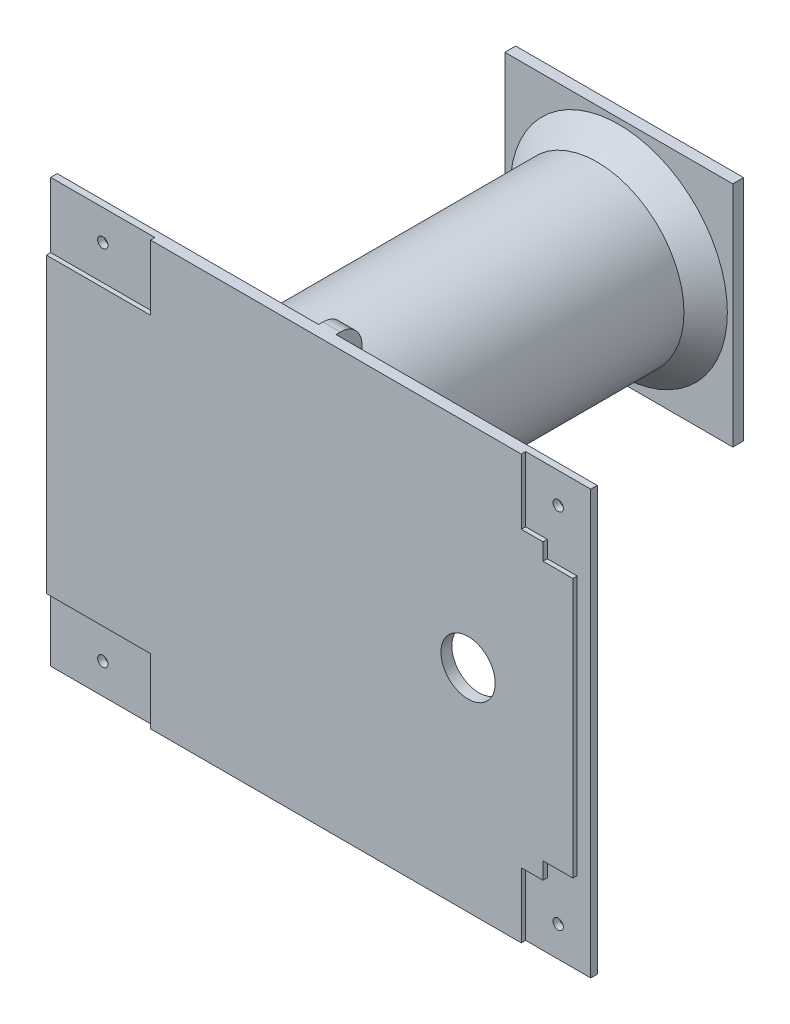
SolidWorks part; units mm, degrees
ref_plane "Alzado" through (0, 0, 0) normal (0, 0, 1) x (1, 0, 0)
ref_plane "Planta" through (0, 0, 0) normal (0, 1, 0) x (1, 0, 0)
ref_plane "Vista lateral" through (0, 0, 0) normal (1, 0, 0) x (0, 0, -1)
sketch "Croquis1" plane through (0, 0, 0) normal (0, 0, 1) x (1, 0, 0)
  line L1 (-117.2917, 97.7627) -> (131.4683, 97.7627)
  line L2 (-117.2917, 97.7627) -> (-117.2917, -97.2373)
  line L3 (-117.2917, -97.2373) -> (131.4683, -97.2373)
  line L4 (131.4683, 97.7627) -> (131.4683, -97.2373)
  dimension "D1" = 248.76
  dimension "D2" = 195
extrude "Saliente-Extruir1" add sketch "Croquis1" along normal blind 5
sketch "Croquis2" plane through (0, 0, 5) normal (0, 0, 1) x (1, 0, 0)
  line L0 (-117.2917, 0.2627) -> (131.4683, 0.2627) construction
  line L1 (-117.2917, 97.7627) -> (-117.2917, -97.2373) construction
  line L2 (131.4683, -97.2373) -> (131.4683, 97.7627) construction
  line L3 (-117.2917, -97.2373) -> (-69.2917, -97.2373)
  line L4 (-117.2917, -97.2373) -> (131.4683, -97.2373) construction
  line L5 (-69.2917, -97.2373) -> (-69.2917, -67.2373)
  line L6 (-69.2917, -67.2373) -> (-117.2917, -67.2373)
  line L7 (-117.2917, -67.2373) -> (-117.2917, -97.2373)
  line L8 (131.4683, 67.7627) -> (101.4683, 67.7627)
  line L9 (131.4683, -97.2373) -> (101.4683, -97.2373)
  line L10 (131.4683, -97.2373) -> (131.4683, -67.2373)
  line L11 (131.4683, -67.2373) -> (101.4683, -67.2373)
  line L12 (101.4683, -97.2373) -> (101.4683, -67.2373)
  line L13 (101.4683, 97.7627) -> (101.4683, 67.7627)
  line L14 (131.4683, 97.7627) -> (101.4683, 97.7627)
  line L15 (131.4683, 97.7627) -> (131.4683, 67.7627)
  line L16 (-69.2917, 67.7627) -> (-117.2917, 67.7627)
  line L17 (-69.2917, 97.7627) -> (-69.2917, 67.7627)
  line L18 (-117.2917, 97.7627) -> (-69.2917, 97.7627)
  line L19 (-117.2917, 67.7627) -> (-117.2917, 97.7627)
  dimension "D1" = 48
  dimension "D2" = 30
  dimension "D3" = 30
  dimension "D4" = 30
extrude "Cortar-Extruir1" cut sketch "Croquis2" against normal blind 2
sketch "Croquis3" plane through (0, 0, 5) normal (0, 0, 1) x (1, 0, 0)
  line L0 (-69.2917, 97.7627) -> (-117.2917, 97.7627) construction
  line L1 (116.4683, 83.7627) -> (116.4683, 67.7627) construction
  line L3 (116.4683, -83.2373) -> (116.4683, -67.2373) construction
  line L5 (131.4683, -67.2373) -> (101.4683, -67.2373) construction
  line L6 (101.4683, 67.7627) -> (131.4683, 67.7627) construction
  line L7 (-93.2917, 83.7627) -> (-93.2917, 67.7627) construction
  line L8 (-117.2917, 67.7627) -> (-69.2917, 67.7627) construction
  line L9 (-93.2917, -83.2373) -> (-93.2917, -67.2373) construction
  line L10 (-69.2917, -67.2373) -> (-117.2917, -67.2373) construction
  circle A0 centre (-93.2917, 83.7627) radius 2.375
  circle A1 centre (-93.2917, -83.2373) radius 2.375
  circle A2 centre (116.4683, 83.7627) radius 2.375
  circle A3 centre (116.4683, -83.2373) radius 2.375
  dimension "D2" = 4.75
  dimension "D3" = 4.75
  dimension "D5" = 4.75
  dimension "D6" = 4.75
  dimension "D1" = 14
  dimension "D4" = 14
  dimension "D7" = 209.76
  dimension "D8" = 16
  dimension "D9" = 16
extrude "Cortar-Extruir2" cut sketch "Croquis3" against normal blind 10
sketch "Croquis4" plane through (0, 0, 0) normal (0, 0, -1) x (-1, 0, 0)
  line L7 (-131.4683, 97.7627) -> (117.2917, 97.7627) construction
  line L9 (117.2917, 97.7627) -> (117.2917, -97.2373) construction
  circle A0 centre (55.1017, 0.2627) radius 40
  dimension "D3" = 80
  dimension "D1" = 62.19
  dimension "D2" = 97.5
extrude "Saliente-Extruir2" add sketch "Croquis4" along normal blind 196.5 contours A0
sketch "Croquis5" plane through (0, 0, 0) normal (0, 0, -1) x (-1, 0, 0)
  line L0 (-131.4683, 0.2627) -> (117.2917, 0.2627) construction
  line L1 (-131.4683, -97.2373) -> (-131.4683, 97.7627) construction
  line L2 (117.2917, 97.7627) -> (117.2917, -97.2373) construction
  circle A0 centre (-76.9683, 0.2627) radius 12.5
  dimension "D1" = 25
  dimension "D2" = 54.5
extrude "Cortar-Extruir3" cut sketch "Croquis5" against normal blind 10
sketch "Croquis6" plane through (0, 0, 0) normal (0, 0, -1) x (-1, 0, 0)
  line L0 (-131.4683, 97.7627) -> (117.2917, 97.7627) construction
  line L1 (-7.0883, 97.7627) -> (-7.0883, -97.2373)
  line L2 (117.2917, -97.2373) -> (-131.4683, -97.2373) construction
  line L3 (-7.0883, 97.7627) -> (117.2917, 97.7627)
  line L4 (117.2917, 97.7627) -> (117.2917, -97.2373)
  line L5 (117.2917, -97.2373) -> (-7.0883, -97.2373)
  line L6 (-131.4683, 0.2627) -> (56.0317, 0.2627)
  line L7 (-131.4683, -97.2373) -> (-131.4683, 97.7627) construction
  circle A1 centre (56.0317, 0.2627) radius 100
  dimension "D1" = 200
  dimension "D2" = 187.5
sketch "Croquis9" plane through (0, 97.7627, 0) normal (0, 1, 0) x (1, 0, 0)
  line L0 (7.0883, 0) -> (7.0883, -5)
  line L1 (131.4683, 0) -> (-117.2917, 0) construction
  line L2 (101.4683, -5) -> (-69.2917, -5) construction
ref_plane "Plano3" through (7.0883, 0, 0) normal (1, 0, 0) x (0, 0, -1)
sketch "Croquis12" plane through (7.0883, 0, 0) normal (1, 0, 0) x (0, 0, -1)
  line L0 (0, 97.7627) -> (0, 67.7627)
  line L1 (0, 67.7627) -> (12, 67.7627)
  line L2 (12, 67.7627) -> (12, 97.7627)
  line L3 (12, 97.7627) -> (0, 97.7627)
  line L4 (0, -97.2373) -> (12, -97.2373)
  line L5 (12, -97.2373) -> (12, -67.2373)
  line L6 (12, -67.2373) -> (0, -67.2373)
  line L7 (0, -67.2373) -> (0, -97.2373)
  dimension "D1" = 30
  dimension "D2" = 12
  dimension "D3" = 30
  dimension "D4" = 12
extrude "Saliente-Extruir3" add sketch "Croquis12" along normal mid plane 8
fillet "Redondeo1" radius 10 2 edges at (7.0883, -67.2373, 0) (7.0883, 67.7627, 0)
fillet "Redondeo2" radius 10 2 edges at (7.0883, 67.7627, -12) (7.0883, -67.2373, -12)
fillet "Redondeo3" radius 10 2 edges at (7.0883, -97.2373, -12) (7.0883, 97.7627, -12)
sketch "Croquis13" plane through (11.0883, 0, 0) normal (1, 0, 0) x (0, 0, -1)
  line L0 (-5, 0.2627) -> (196.5, 0.2627) construction
  line L1 (-5, -67.2373) -> (-5, 67.7627) construction
  line L2 (196.5, -39.7373) -> (196.5, 40.2627) construction
  line L3 (6, 87.7627) -> (12, 87.7627) construction
  line L4 (6, 87.7627) -> (6, 77.7627) construction
  circle A0 centre (6, 87.7627) radius 1.625
  circle A1 centre (6, 77.7627) radius 1.625
  circle A2 centre (6, -77.2373) radius 1.625
  circle A3 centre (6, -87.2373) radius 1.625
  dimension "D3" = 3.25
  dimension "D4" = 3.25
  dimension "D1" = 6
extrude "Cortar-Extruir5" cut sketch "Croquis13" against normal through all both and the other way through all
sketch "Croquis14" plane through (0, 0, 0) normal (0, 0, -1) x (-1, 0, 0)
  line L0 (-7.0883, 97.7627) -> (-7.0883, -97.2373)
  line L1 (-7.0883, 97.7627) -> (117.2917, 97.7627)
  line L2 (117.2917, 97.7627) -> (117.2917, -97.2373)
  line L3 (117.2917, -97.2373) -> (-7.0883, -97.2373)
sketch "Croquis15" plane through (0, 0, 5) normal (0, 0, 1) x (1, 0, 0)
  line L0 (111.4683, 67.7627) -> (131.4683, 67.7627)
  line L1 (111.4683, 67.7627) -> (111.4683, 60.0127)
  line L2 (131.4683, -67.2373) -> (101.4683, -67.2373) construction
  line L3 (111.4683, -67.2373) -> (111.4683, -59.4873)
  line L4 (111.4683, -59.4873) -> (125.2183, -59.4873)
  line L5 (125.2183, -59.4873) -> (125.2183, 60.0127)
  line L6 (111.4683, 60.0127) -> (125.2183, 60.0127)
  line L7 (111.4683, -67.2373) -> (131.4683, -67.2373)
  line L10 (131.4683, -67.2373) -> (131.4683, 67.7627)
  dimension "D1" = 119.5
  dimension "D2" = 7.75
  dimension "D3" = 13.75
extrude "Cortar-Extruir7" cut sketch "Croquis15" against normal blind 2
sketch "Croquis16" plane through (0, 0, -196.5) normal (0, 0, -1) x (-1, 0, 0)
  line L1 (2.6017, -52.2373) -> (107.6017, -52.2373)
  line L2 (2.6017, -52.2373) -> (2.6017, 52.7627)
  line L3 (2.6017, 52.7627) -> (107.6017, 52.7627)
  line L4 (107.6017, -52.2373) -> (107.6017, 52.7627)
  line L5 (2.6017, -52.2373) -> (107.6017, 52.7627) construction
  line L6 (2.6017, 52.7627) -> (107.6017, -52.2373) construction
  point P0 (55.1017, 0.2627)
  dimension "D1" = 105
  dimension "D2" = 105
extrude "Saliente-Extruir4" add sketch "Croquis16" along normal blind 5
fillet "Chaflán1" radius 10 1 edges at (-95.1017, 0.2627, -196.5) type face fillet profile chamfer first side face at (-95.1017, 0.2627, -196.5) second side face at (-95.1017, 0.2627, -196.5)
